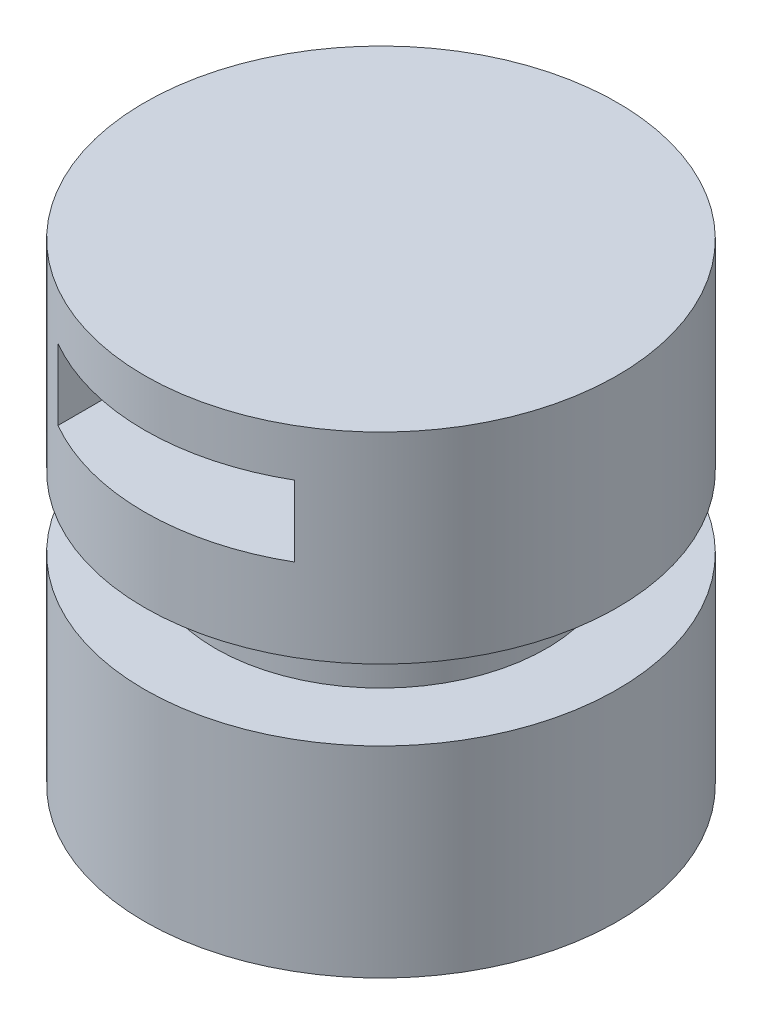
SolidWorks part; units mm, degrees
ref_plane "Front Plane" through (0, 0, 0) normal (0, 0, 1) x (1, 0, 0)
ref_plane "Top Plane" through (0, 0, 0) normal (0, 1, 0) x (1, 0, 0)
ref_plane "Right Plane" through (0, 0, 0) normal (1, 0, 0) x (0, 0, -1)
sketch "Sketch2" plane through (0, 0, 0) normal (0, 1, 0) x (1, 0, 0)
  circle A0 centre (0, 0) radius 100
  dimension "D1" = 200
extrude "Boss-Extrude1" add sketch "Sketch2" along normal blind 200
sketch "Sketch3" plane through (0, 0, 0) normal (0, 0, 1) x (1, 0, 0)
  line L0 (100, 200) -> (100, 100) construction
  line L1 (100, 0) -> (100, 200) construction
  line L2 (100, 100) -> (100, 115)
  line L3 (100, 115) -> (70, 115)
  line L4 (70, 115) -> (70, 85)
  line L5 (70, 85) -> (100, 85)
  line L6 (100, 85) -> (100, 115)
  line L7 (-100, 200) -> (100, 200) construction
  line L8 (100, 200) -> (-100, 200) construction
  line L9 (0, 200) -> (0, 235.1705) construction
  line L10 (0, 235.1705) -> (0, -20.0808) construction
  dimension "D1" = 30
revolve "Cut-Revolve3" cut sketch "Sketch3" angle 360 about L10 region at (85, 100, 0)
sketch "Sketch4" plane through (0, 0, 0) normal (0, 0, 1) x (1, 0, 0)
  line L0 (0, 203.033) -> (0, -10.1781) construction
  line L1 (0, 200) -> (0, 180) construction
  line L2 (100, 200) -> (-100, 200) construction
  line L3 (0, 180) -> (50, 180)
  line L4 (50, 180) -> (50, 150)
  line L5 (50, 150) -> (-50, 150)
  line L6 (-50, 150) -> (-50, 180)
  line L7 (-50, 180) -> (0, 180)
  dimension "D1" = 20
  dimension "D2" = 30
extrude "Cut-Extrude1" cut sketch "Sketch4" against normal blind 200 and the other way blind 200 contours L7 L3 L4 L5 L6
